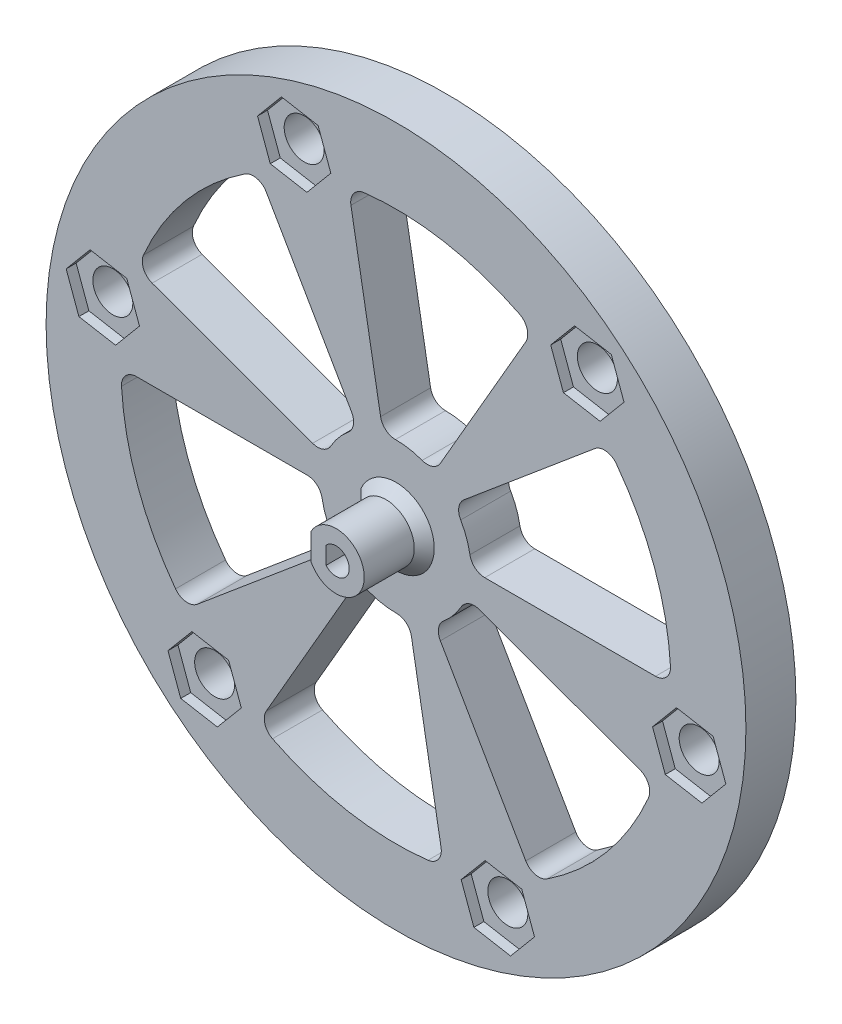
SolidWorks part; units mm, degrees
material "6061-T6 (SS)"
ref_plane "Plan de face" through (0, 0, 0) normal (0, 0, 1) x (1, 0, 0)
ref_plane "Plan de dessus" through (0, 0, 0) normal (0, 1, 0) x (1, 0, 0)
ref_plane "Plan de droite" through (0, 0, 0) normal (1, 0, 0) x (0, 0, -1)
sketch "Esquisse1" plane through (0, 0, 0) normal (0, 0, 1) x (1, 0, 0)
  circle A0 centre (0, 0) radius 70
  dimension "D1" = 140
extrude "Boss.-Extru.1" add sketch "Esquisse1" along normal blind 10
sketch "Esquisse2" plane through (0, 0, 10) normal (0, 0, 1) x (1, 0, 0)
  line L0 (-2, 1.7385) -> (-2, -1.7385)
  arc A0 (-2, 1.7385) -> (-2, -1.7385) centre (0, 0) cw
  point P5 (2.65, 0)
  dimension "D1" = 2.65
  dimension "D2" = 4.65
extrude "Enlèv. mat.-Extru.1" cut sketch "Esquisse2" against normal through all
sketch "Esquisse3" plane through (0, 0, 10) normal (0, 0, 1) x (1, 0, 0)
  line L0 (-2, 1.7385) -> (-2, -1.7385) construction
  line L1 (-2, 1.7385) -> (-2, -1.7385)
  line L2 (-5, 2.6311) -> (-5, -2.6311)
  arc A0 (-2, -1.7385) -> (-2, 1.7385) centre (0, 0) ccw construction
  arc A1 (-2, -1.7385) -> (-2, 1.7385) centre (0, 0) ccw
  arc A2 (-5, -2.6311) -> (-5, 2.6311) centre (0, 0) ccw
  dimension "D1" = 3
extrude "Boss.-Extru.2" add sketch "Esquisse3" along normal blind 12
sketch "Esquisse4" plane through (-5, 0, 0) normal (-1, 0, 0) x (0, 0, 1)
  line L0 (22, 2.6311) -> (10, 2.6311) construction
  line L1 (22, 2.6311) -> (22, -2.6311) construction
  circle A0 centre (16, 0) radius 1.5
  point P5 (16, 2.6311)
  point P8 (22, 0)
  dimension "D1" = 3
extrude "Enlèv. mat.-Extru.2" cut sketch "Esquisse4" against normal up to next
chamfer "Chanfrein1" distance 2 angle 45 2 edges at (-5, 0, 10) (5.65, 0, 10)
sketch "Esquisse5" plane through (0, 0, 10) normal (0, 0, 1) x (1, 0, 0)
  line L0 (0, 0) -> (70, 0) construction
  line L1 (0, 0) -> (35, -60.6218) construction
  line L2 (0, 0) -> (65.7785, -23.9414) construction
  line L3 (14.0954, -5.1303) -> (51.6831, -18.8111)
  line L4 (7.5, -12.9904) -> (27.5, -47.6314)
  circle A0 centre (0, 0) radius 70 construction
  arc A1 (51.6831, -18.8111) -> (27.5, -47.6314) centre (0, 0) cw
  arc A2 (14.0954, -5.1303) -> (7.5, -12.9904) centre (0, 0) cw
  dimension "D1" = 60
  dimension "D2" = 20
  dimension "D3" = 15
  dimension "D4" = 15
extrude "Enlèv. mat.-Extru.3" cut sketch "Esquisse5" against normal up to next
fillet "Congé1" radius 3 4 edges at (27.5, -47.6314, 5) (51.6831, -18.8111, 5) (7.5, -12.9904, 5) (14.0954, -5.1303, 5)
sketch "Esquisse7" plane through (0, 0, 10) normal (0, 0, 1) x (1, 0, 0)
  line L0 (0, 0) -> (68.9365, -12.1554) construction
  line L1 (65.9821, -11.6344) -> (63.4348, -4.6358)
  line L2 (63.4348, -4.6358) -> (56.1001, -3.3425)
  line L3 (56.1001, -3.3425) -> (51.3128, -9.0478)
  line L4 (51.3128, -9.0478) -> (53.8601, -16.0465)
  line L5 (53.8601, -16.0465) -> (61.1948, -17.3398)
  line L6 (61.1948, -17.3398) -> (65.9821, -11.6344)
  line L7 (48.7826, -17.7554) -> (16.6779, -6.0703) construction
  circle A0 centre (58.6475, -10.3411) radius 6.45 construction
  circle A1 centre (0, 0) radius 70 construction
  dimension "D1" = 12.9
  dimension "D2" = 3
  dimension "D3" = 10
extrude "Enlèv. mat.-Extru.4" cut sketch "Esquisse7" against normal blind 2
sketch "Esquisse8" plane through (0, 0, 8) normal (0, 0, 1) x (1, 0, 0)
  line L0 (56.1001, -3.3425) -> (61.1948, -17.3398) construction
  circle A0 centre (58.6475, -10.3411) radius 4
  dimension "D1" = 8
extrude "Enlèv. mat.-Extru.5" cut sketch "Esquisse8" against normal up to next
ref_axis "Axe1" through (0, 0, -0.8) along (0, 0, 1)
pattern_circular "Répétition circulaire1" count 6 over 360 about axis through (0, 0, -0.8) along (0, 0, 1) of "Congé1", "Enlèv. mat.-Extru.3", "Enlèv. mat.-Extru.4", "Enlèv. mat.-Extru.5"
equation "\"____ GENERATED PART EXPORTS ____\" = 0"
equation "\"SYS_VersionTag\" = 2"
equation "\"WHL_WheelOD\" = 140mm"
equation "\"WHL_WheelID\" = 100mm"
equation "\"WHL_WheelThk\" = 10mm"
equation "\"WHL_WheelRadius\" = 70mm"
equation "\"D1@Esquisse1\"=\"WHL_WheelOD\""
equation "\"D1@Boss.-Extru.1\"=\"WHL_WheelThk\""
